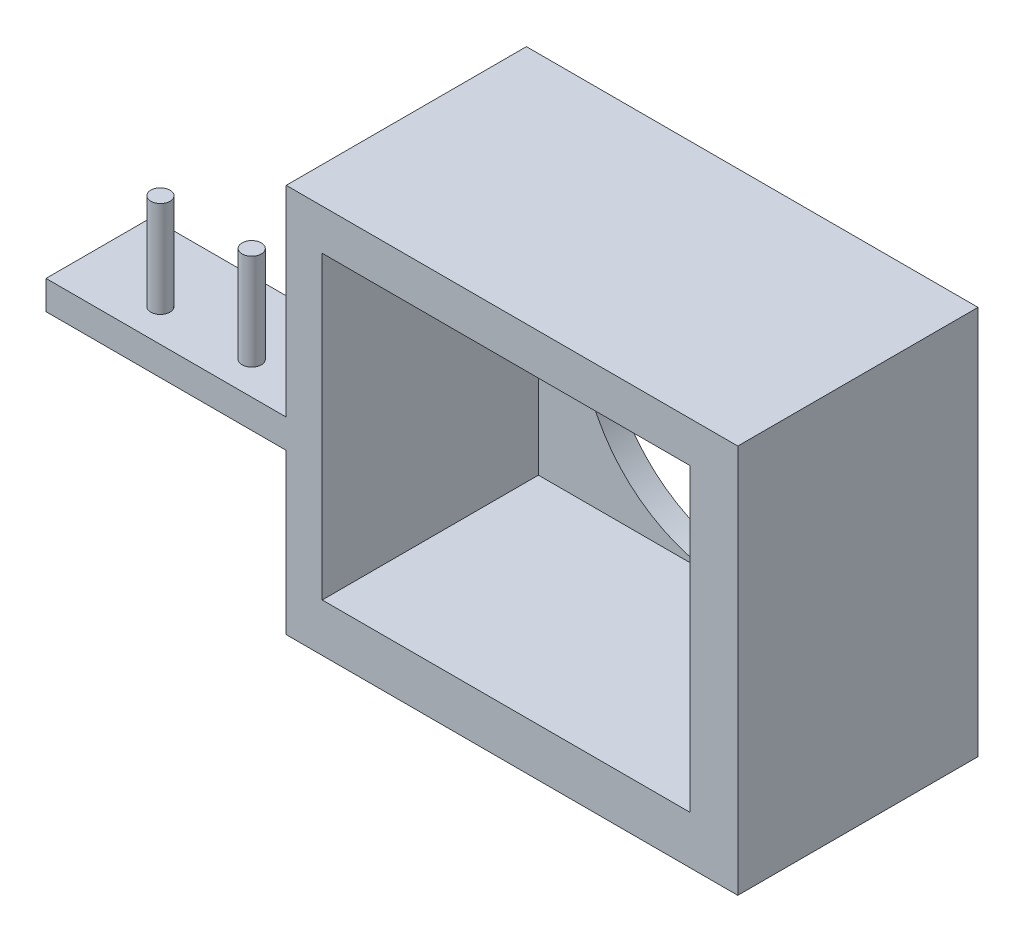
SolidWorks part; units mm, degrees
ref_plane "Alzado" through (0, 0, 0) normal (0, 0, 1) x (1, 0, 0)
ref_plane "Planta" through (0, 0, 0) normal (0, 1, 0) x (1, 0, 0)
ref_plane "Vista lateral" through (0, 0, 0) normal (1, 0, 0) x (0, 0, -1)
ref_plane "Plano1" through (0, 0, 25) normal (0, 0, 1) x (1, 0, 0)
sketch "Croquis1" plane through (0, 0, 25) normal (0, 0, 1) x (1, 0, 0)
  line L0 (-45.7431, 54.4363) -> (-45.7431, 13.9363)
  line L1 (-45.7431, 13.9363) -> (1.2569, 13.9363)
  line L2 (1.2569, 13.9363) -> (1.2569, 54.4363)
  line L3 (1.2569, 54.4363) -> (-45.7431, 54.4363)
extrude "Saliente-Extruir1" add sketch "Croquis1" against normal blind 25
sketch "Croquis2" plane through (-45.7431, 0, 0) normal (-1, 0, 0) x (0, 0, 1)
  line L0 (25, 30.5463) -> (14.0661, 30.5463)
  line L1 (14.0661, 30.5463) -> (14.0661, 33.5463)
  line L2 (14.0661, 33.5463) -> (25, 33.5463)
  line L3 (25, 33.5463) -> (25, 30.5463)
extrude "Saliente-Extruir2" add sketch "Croquis2" along normal blind 25
sketch "Croquis3" plane through (0, 0, 25) normal (0, 0, 1) x (1, 0, 0)
  line L0 (-3.7431, 50.1863) -> (-41.9931, 50.1863)
  line L1 (-41.9931, 50.1863) -> (-41.9931, 18.9363)
  line L2 (-41.9931, 18.9363) -> (-3.7431, 18.9363)
  line L3 (-3.7431, 18.9363) -> (-3.7431, 50.1863)
  dimension "D1" = 31.25
  dimension "D2" = 38.25
extrude "Cortar-Extruir1" cut sketch "Croquis3" against normal blind 22.5
ref_plane "Plano2" through (0, 0, 21.5904) normal (0, 0, 1) x (1, 0, 0)
sketch "Croquis4" plane through (0, 0, 21.5904) normal (0, 0, 1) x (1, 0, 0)
  line L0 (-51.7431, 43.5463) -> (-52.7431, 43.5463)
  line L1 (-52.7431, 43.5463) -> (-52.7431, 33.5463)
  line L2 (-52.7431, 33.5463) -> (-51.7431, 33.5463)
  line L3 (-51.7431, 33.5463) -> (-51.7431, 43.5463)
  line L4 (-52.7431, 43.5463) -> (-52.7431, 33.5463) construction
revolve "Revolución1" add sketch "Croquis4" angle 360 about L4 reverse direction yes
sketch "Croquis5" plane through (0, 0, 21.5904) normal (0, 0, 1) x (1, 0, 0)
  line L0 (-61.2431, 43.5463) -> (-62.2431, 43.5463)
  line L1 (-62.2431, 43.5463) -> (-62.2431, 33.5463)
  line L2 (-62.2431, 33.5463) -> (-61.2431, 33.5463)
  line L3 (-61.2431, 33.5463) -> (-61.2431, 43.5463)
  line L4 (-62.2431, 43.5463) -> (-62.2431, 33.5463) construction
revolve "Revolución2" add sketch "Croquis5" angle 360 about L4 reverse direction yes
sketch "Croquis6" plane through (0, 0, 0) normal (0, 0, -1) x (-1, 0, 0)
  circle A0 centre (22.2431, 34.1863) radius 15.25
  dimension "D1" = 30.5
extrude "Cortar-Extruir2" cut sketch "Croquis6" against normal blind 10
